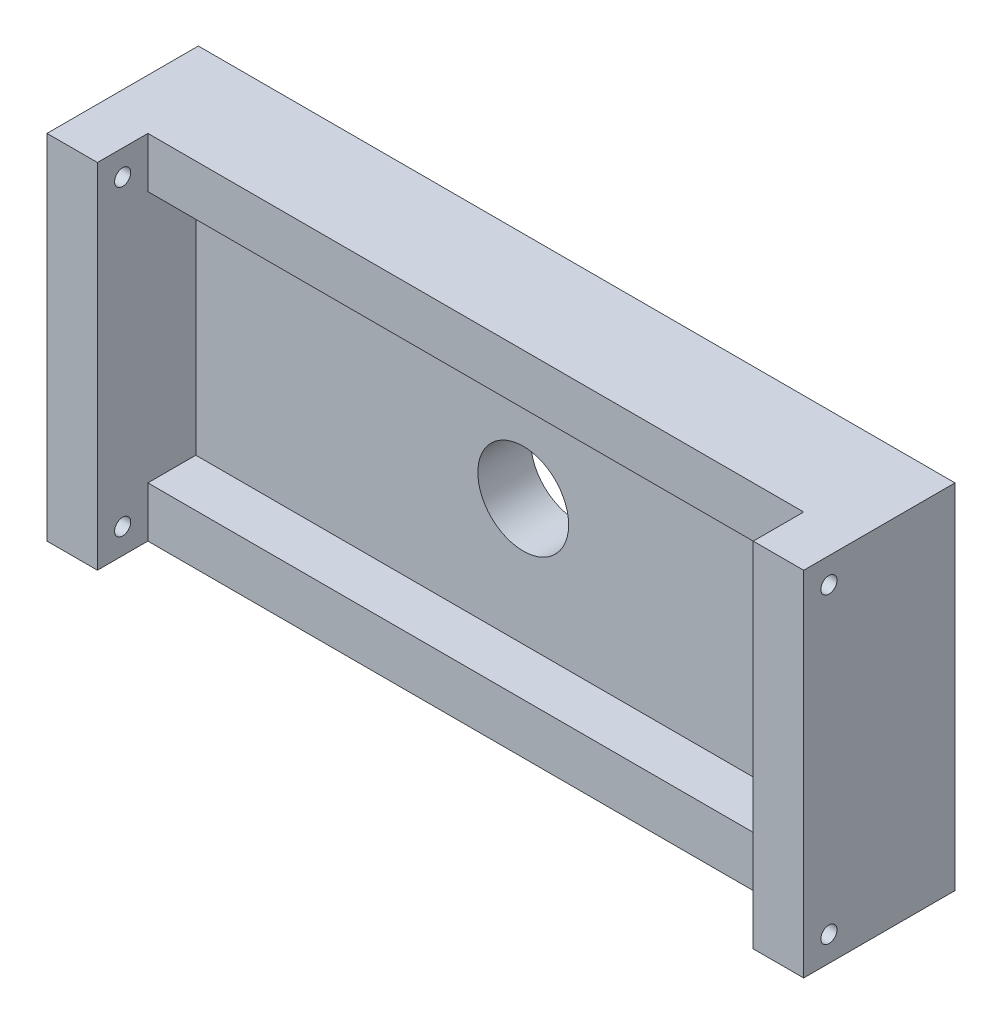
SolidWorks part; units mm, degrees
ref_plane "Front Plane" through (0, 0, 0) normal (0, 0, 1) x (1, 0, 0)
ref_plane "Top Plane" through (0, 0, 0) normal (0, 1, 0) x (1, 0, 0)
ref_plane "Right Plane" through (0, 0, 0) normal (1, 0, 0) x (0, 0, -1)
sketch "Sketch1" plane through (0, 0, 0) normal (0, 1, 0) x (1, 0, 0)
  line L0 (-75, 0) -> (75, 0)
  line L1 (75, 0) -> (75, 30)
  line L2 (75, 30) -> (69.5, 30)
  line L3 (-75, 30) -> (-75, 0)
  line L4 (-69.5, 30) -> (-75, 30)
  line L5 (45.5, 30) -> (-45.5, 30)
  line L6 (-69.5, 42) -> (-69.5, 30)
  line L7 (-45.5, 42) -> (-45.5, 30)
  line L8 (45.5, 42) -> (45.5, 30)
  line L9 (69.5, 42) -> (69.5, 30)
  line L10 (-57.5, 42) -> (57.5, 42) construction
  line L11 (-57.5, 42) -> (0, 0) construction
  line L12 (57.5, 42) -> (0, 0) construction
  arc A1 (-45.5, 42) -> (-69.5, 42) centre (-57.5, 42) ccw
  arc A2 (69.5, 42) -> (45.5, 42) centre (57.5, 42) ccw
  circle A3 centre (57.5, 42) radius 5
  circle A4 centre (-57.5, 42) radius 5
  dimension "D5" = 24
  dimension "D7" = 10
  dimension "D1" = 30
  dimension "D2" = 150
  dimension "D3" = 75
  dimension "D4" = 115
extrude "Boss-Extrude1" add sketch "Sketch1" along normal blind 70
sketch "Sketch2" plane through (0, 0, 0) normal (0, 0, 1) x (1, 0, 0)
  line L8 (-75, 0) -> (75, 0)
  line L9 (75, 0) -> (75, 70)
  line L10 (75, 70) -> (-75, 70)
  line L11 (-75, 70) -> (-75, 0)
  line L12 (-75, 0) -> (75, 0)
  line L13 (75, 0) -> (75, 70)
  line L14 (75, 70) -> (-75, 70)
  line L15 (-75, 70) -> (-75, 0)
  dimension "D1" = 0
sketch "Sketch3" plane through (-75, 0, 0) normal (-1, 0, 0) x (0, 0, 1)
  line L0 (-30, 0) -> (-80, 0)
  line L1 (-80, 0) -> (-80, 30)
  line L2 (-80, 30) -> (-30, 30)
  line L3 (-30, 70) -> (-30, 0) construction
  line L4 (-30, 0) -> (-30, 30)
  dimension "D1" = 30
  dimension "D2" = 50
extrude "Cut-Extrude1" cut sketch "Sketch3" against normal through all contours L4 L2 L1 L0
sketch "Sketch6" plane through (0, 0, 0) normal (0, 0, 1) x (1, 0, 0)
  line L0 (-65, 10) -> (65, 10)
  line L1 (65, 10) -> (65, 60)
  line L2 (65, 60) -> (-65, 60)
  line L3 (-65, 60) -> (-65, 10)
  line L4 (-75, 0) -> (75, 0)
  line L5 (75, 0) -> (75, 70)
  line L6 (75, 70) -> (-75, 70)
  line L7 (-75, 70) -> (-75, 0)
  line L8 (-75, 0) -> (75, 0) construction
  line L9 (75, 0) -> (75, 70) construction
  line L10 (75, 70) -> (-75, 70) construction
  line L11 (-75, 70) -> (-75, 0) construction
  dimension "D1" = 0
  dimension "D2" = 10
extrude "Cut-Extrude2" cut sketch "Sketch6" against normal blind 19.5 contours L0 L1 L2 L3
sketch "Sketch7" plane through (0, 0, -19.5) normal (0, 0, 1) x (1, 0, 0)
  line L0 (-0.0942, 35) -> (65, 35)
  line L4 (-65, 60) -> (-65, 10)
  line L5 (-65, 10) -> (65, 10)
  line L6 (65, 10) -> (65, 60)
  line L7 (65, 60) -> (-65, 60)
  line L8 (-65, 60) -> (-65, 10)
  line L9 (-65, 10) -> (65, 10)
  line L10 (65, 10) -> (65, 60)
  line L11 (65, 60) -> (-65, 60)
  circle A0 centre (-0.0942, 35) radius 9
  dimension "D2" = 18
  dimension "D1" = 0
extrude "Cut-Extrude3" cut sketch "Sketch7" against normal through all contours A0 region at (-8.8397, 35, -19.5)
sketch "Sketch8" plane through (75, 0, 0) normal (1, 0, 0) x (0, 0, -1)
  line L0 (30, 70) -> (64.8307, 70)
  line L1 (64.8307, 70) -> (64.8307, 0)
  line L2 (64.8307, 0) -> (30, 0)
  line L3 (30, 0) -> (30, 70)
extrude "Cut-Extrude4" cut sketch "Sketch8" against normal through all
sketch "Sketch9" plane through (0, 70, 0) normal (0, 1, 0) x (1, 0, 0)
  line L0 (-65, 0) -> (-65, 10)
  line L1 (-75, 0) -> (75, 0) construction
  line L2 (-65, 10) -> (65, 10)
  line L3 (65, 10) -> (65, 0)
  line L4 (75, 0) -> (-75, 0) construction
  line L5 (65, 0) -> (-65, 0)
  line L6 (-75, 30) -> (-75, 0) construction
  line L7 (75, 0) -> (75, 30) construction
  dimension "D1" = 10
  dimension "D2" = 10
  dimension "D3" = 10
extrude "Cut-Extrude5" cut sketch "Sketch9" against normal through all
sketch "Sketch12" plane through (65, 0, 0) normal (-1, 0, 0) x (0, 0, 1)
  line L0 (-10, 70) -> (0, 70) construction
  line L1 (0, 70) -> (0, 0) construction
  line L2 (0, 0) -> (-10, 0) construction
  line L3 (-10, 0) -> (-10, 70) construction
  line L4 (-5, 70) -> (-5, 0) construction
  line L5 (-10, 35) -> (0, 35) construction
  circle A0 centre (-5, 65) radius 1.6
  circle A1 centre (-5, 5) radius 1.6
  dimension "D3" = 3.2
  dimension "D1" = 5
  dimension "D2" = 5
extrude "Cut-Extrude6" cut sketch "Sketch12" against normal through all both and the other way through all
